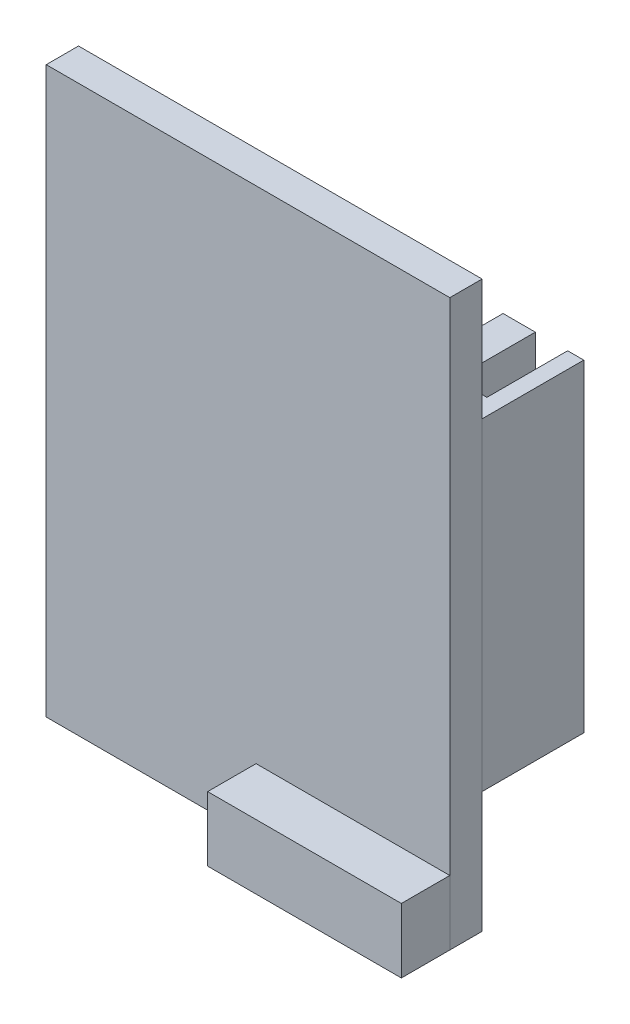
SolidWorks part; units mm, degrees
ref_plane "Alzado" through (0, 0, 0) normal (0, 0, 1) x (1, 0, 0)
ref_plane "Planta" through (0, 0, 0) normal (0, 1, 0) x (1, 0, 0)
ref_plane "Vista lateral" through (0, 0, 0) normal (1, 0, 0) x (0, 0, -1)
sketch "Croquis1" plane through (0, 0, 0) normal (0, 0, 1) x (1, 0, 0)
  line L1 (-40.6526, 11.9444) -> (-15.6526, 11.9444)
  line L2 (-40.6526, 11.9444) -> (-40.6526, -23.0556)
  line L3 (-40.6526, -23.0556) -> (-15.6526, -23.0556)
  line L4 (-15.6526, 11.9444) -> (-15.6526, -23.0556)
  dimension "D1" = 25
  dimension "D2" = 35
extrude "Saliente-Extruir1" add sketch "Croquis1" along normal blind 2
sketch "Croquis2" plane through (0, 0, 2) normal (0, 0, 1) x (1, 0, 0)
  line L1 (-15.6526, -23.0556) -> (-27.6526, -23.0556)
  line L2 (-15.6526, -23.0556) -> (-15.6526, -19.0556)
  line L3 (-15.6526, -19.0556) -> (-27.6526, -19.0556)
  line L4 (-27.6526, -23.0556) -> (-27.6526, -19.0556)
  dimension "D1" = 4
  dimension "D2" = 12
extrude "Saliente-Extruir2" add sketch "Croquis2" along normal blind 3
sketch "Croquis4" plane through (0, 0, 0) normal (0, 0, -1) x (-1, 0, 0)
  line L0 (15.6526, -23.0556) -> (15.6526, 11.9444) construction
  line L1 (15.6526, 4.4444) -> (40.6526, 4.4444)
  line L2 (15.6526, 4.4444) -> (15.6526, -15.5556)
  line L3 (15.6526, -15.5556) -> (40.6526, -15.5556)
  line L4 (40.6526, 4.4444) -> (40.6526, -15.5556)
  line L5 (40.6526, 11.9444) -> (40.6526, -23.0556) construction
  line L6 (15.6526, 11.9444) -> (40.6526, 11.9444) construction
  dimension "D1" = 20
  dimension "D2" = 7.5
extrude "Saliente-Extruir3" add sketch "Croquis4" along normal blind 6.3
sketch "Croquis5" plane through (0, 4.4444, 0) normal (0, 1, 0) x (1, 0, 0)
  line L0 (-40.6526, 6.3) -> (-15.6526, 6.3) construction
  line L1 (-16.6526, 6.3) -> (-18.6526, 6.3)
  line L2 (-16.6526, 6.3) -> (-16.6526, 1.3)
  line L3 (-16.6526, 1.3) -> (-18.6526, 1.3)
  line L4 (-18.6526, 6.3) -> (-18.6526, 1.3)
  line L5 (-15.6526, 6.3) -> (-15.6526, 0) construction
  line L6 (-40.6526, 0) -> (-15.6526, 0) construction
  line L7 (-20.6526, 6.3) -> (-22.6526, 6.3)
  line L8 (-20.6526, 6.3) -> (-20.6526, 1.3)
  line L9 (-20.6526, 1.3) -> (-22.6526, 1.3)
  line L10 (-22.6526, 6.3) -> (-22.6526, 1.3)
  line L11 (-24.6526, 6.3) -> (-26.6526, 6.3)
  line L12 (-24.6526, 6.3) -> (-24.6526, 1.3)
  line L13 (-24.6526, 1.3) -> (-26.6526, 1.3)
  line L14 (-26.6526, 6.3) -> (-26.6526, 1.3)
  line L15 (-28.6526, 6.3) -> (-30.6526, 6.3)
  line L16 (-28.6526, 6.3) -> (-28.6526, 1.3)
  line L17 (-28.6526, 1.3) -> (-30.6526, 1.3)
  line L18 (-30.6526, 6.3) -> (-30.6526, 1.3)
  line L19 (-32.6526, 6.3) -> (-34.6526, 6.3)
  line L20 (-32.6526, 6.3) -> (-32.6526, 1.3)
  line L21 (-32.6526, 1.3) -> (-34.6526, 1.3)
  line L22 (-34.6526, 6.3) -> (-34.6526, 1.3)
  line L23 (-36.6526, 6.3) -> (-38.6526, 6.3)
  line L24 (-36.6526, 6.3) -> (-36.6526, 1.3)
  line L25 (-36.6526, 1.3) -> (-38.6526, 1.3)
  line L26 (-38.6526, 6.3) -> (-38.6526, 1.3)
  dimension "D1" = 2
  dimension "D2" = 1
  dimension "D3" = 1.3
  dimension "D4" = 6
extrude "Cortar-Extruir1" cut sketch "Croquis5" against normal up to vertex (20 mm away) up to point (-40.6526, -15.5556, -6.3)
ref_plane "Plano1" through (0, 0, 2) normal (0, 0, 1) x (1, 0, 0)
split "Partir1" bodies to split 104 resulting bodies 106 107 split by face at (-27.9859, -10.0556, 2)
split "Partir2" bodies to split 107 resulting bodies 108 109 split by face at (-28.1526, 8.1944, 0)
